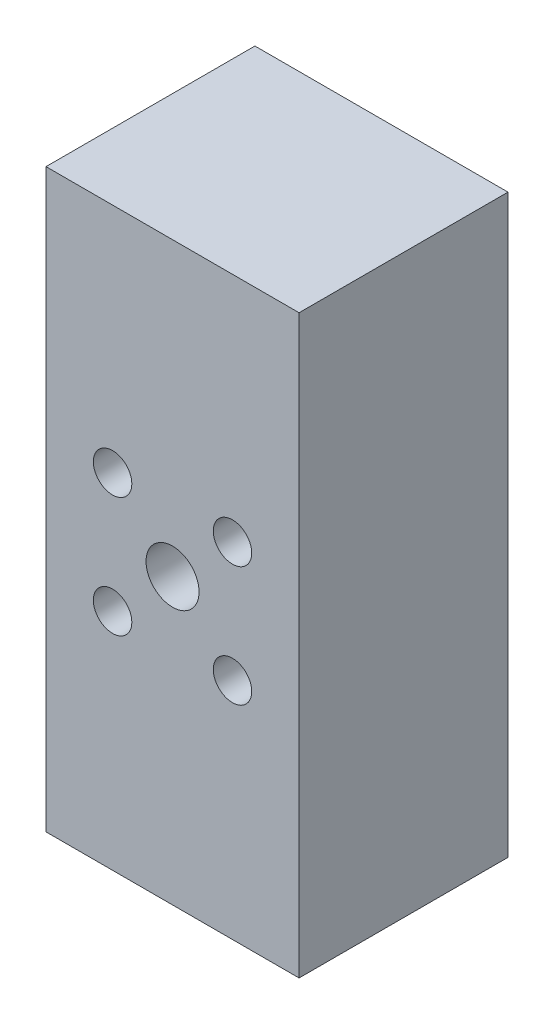
SolidWorks part; units mm, degrees
ref_plane "Front Plane" through (0, 0, 0) normal (0, 0, 1) x (1, 0, 0)
ref_plane "Top Plane" through (0, 0, 0) normal (0, 1, 0) x (1, 0, 0)
ref_plane "Right Plane" through (0, 0, 0) normal (1, 0, 0) x (0, 0, -1)
sketch "Sketch1" plane through (0, 0, 0) normal (0, 1, 0) x (1, 0, 0)
  line L0 (47, 0) -> (47, 38.8)
  line L1 (4.5, 34.4) -> (0, 34.4) construction
  line L2 (42.5, 34.4) -> (47, 34.4) construction
  line B0 (0, 38.8) -> (254, 38.8)
  line B1 (0, 38.8) -> (0, 0)
  line B2 (0, 0) -> (254, 0)
  line B3 (254, 38.8) -> (254, 0)
  circle B4 centre (249.5, 34.4) radius 2.5
  circle B5 centre (249.5, 4.4) radius 2.5
  circle B6 centre (211.5, 4.4) radius 2.5
  circle B7 centre (211.5, 34.4) radius 2.627
  circle B8 centre (42.5, 34.4) radius 2.5
  circle B9 centre (42.5, 4.4) radius 2.5
  circle B10 centre (4.5, 4.4) radius 2.5
  circle B11 centre (4.5, 34.4) radius 2.627
sketch_block_instance "Block-LateralDirSliderMounting-1"
sketch_block "Block-LateralDirSliderMounting"
sketch "Sketch2" plane through (0, 0, 0) normal (0, 0, 1) x (1, 0, 0)
  line L1 (0, 0) -> (47, 0)
  line L2 (0, 0) -> (0, 107)
  line L3 (0, 107) -> (47, 107)
  line L4 (47, 0) -> (47, 107)
  point P5 (12.3645, 38.1)
  point P10 (23.5, 0)
  circle B0 centre (23.5, 52.8074) radius 20.4391
  circle B1 centre (34.6355, 63.9429) radius 3.5719
  circle B2 centre (34.6355, 41.6719) radius 3.5719
  circle B3 centre (12.3645, 41.6719) radius 3.5719
  circle B4 centre (12.3645, 63.9429) radius 3.5719
  circle B5 centre (23.5, 52.8074) radius 4.9213
  dimension "D1" = 107
  dimension "D2" = 38.1
sketch_block_instance "Block-RailTravellerMounting-1"
sketch_block "Block-RailTravellerMounting"
extrude "Boss-Extrude1" add sketch "Sketch1" along normal up to vertex (107 mm away) contours B1 B2 L0 B0 B11 B10 B9 B8 | B9 | B10 | B11 | B8 region at (23.5223, 0, -19.3824) region at (42.5, 0, -34.4) region at (42.5, 0, -4.4) region at (4.5, 0, -4.4) region at (4.5, 0, -34.4) up to point (0, 107, 0)
extrude "Cut-Extrude1" cut sketch "Sketch2" against normal through all contours B4 | B1 | B2 | B5 | B3 region at (34.6355, 63.9429, 0) region at (34.6355, 41.6719, 0) region at (12.3645, 41.6719, 0) region at (12.3645, 63.9429, 0) region at (23.5, 52.8074, 0)
extrude "Cut-Extrude2" cut sketch "Sketch1<8>" along normal blind 38.1 contours B11 | B10 | B9 | B8 region at (42.5, 0, -34.4) region at (42.5, 0, -4.4) region at (4.5, 0, -4.4) region at (4.5, 0, -34.4)
sketch "Sketch1<8>" plane through (0, 0, 0) normal (0, 1, 0) x (1, 0, 0) same geometry as "Sketch1"
sketch "Sketch3" plane through (47, 0, 0) normal (1, 0, 0) x (0, 0, -1)
  line L0 (0, 0) -> (38.8, 0) construction
  line B0 (12.9, 0) -> (25.9, 0)
  line B1 (25.9, 0) -> (25.9, 107)
  line B2 (25.9, 107) -> (12.9, 107)
  line B3 (12.9, 107) -> (12.9, 0)
  circle B4 centre (19.4, 20) radius 2
  circle B5 centre (19.4, 79.944) radius 2
sketch_block_instance "Block-VerticalDirSliderBaseMounting-1"
sketch_block "Block-VerticalDirSliderBaseMounting"
extrude "Cut-Extrude3" cut sketch "Sketch3" along normal blind 25.4 from surface contours B4 | B5 region at (47, 20, -19.4) region at (47, 79.944, -19.4) starting at face at (0, 53.5, -19.4)
sketch "Sketch4" plane through (0, 0, -38.8) normal (0, 0, -1) x (-1, 0, 0)
  circle A0 centre (-23.5, 52.8074) radius 9.525
  dimension "D1" = 19.05
extrude "Cut-Extrude4" cut sketch "Sketch4" against normal blind 21.0185
